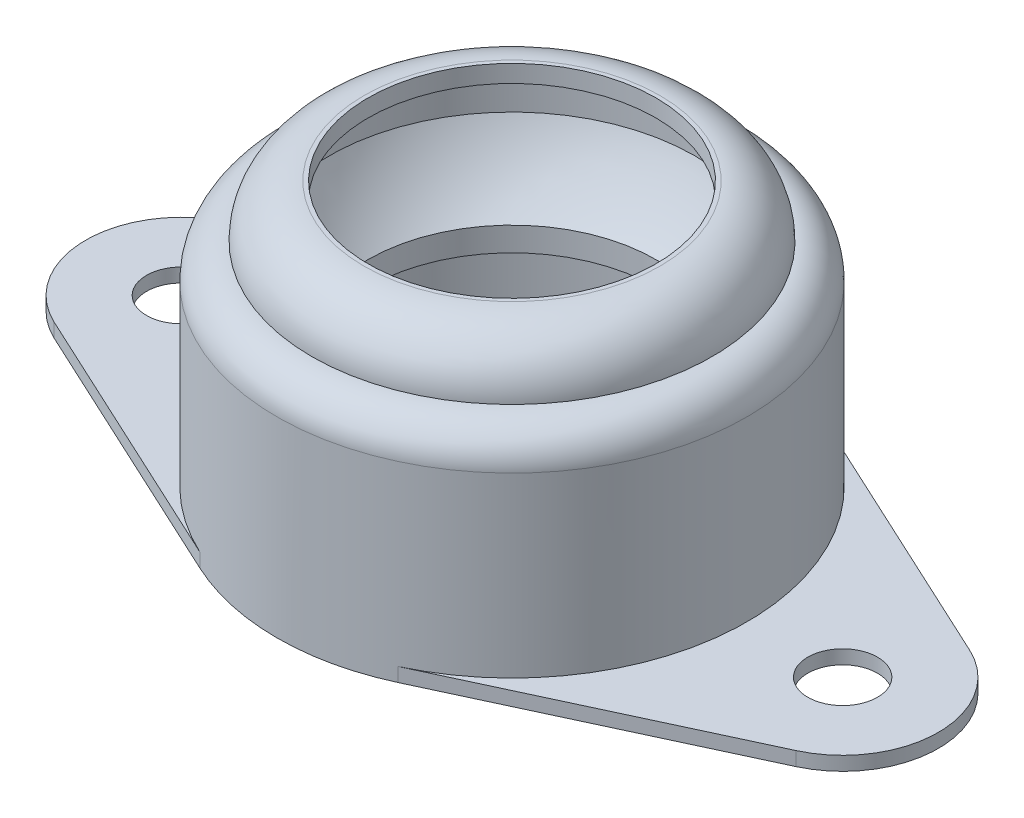
SolidWorks part; units mm, degrees
ref_plane "前视基准面" through (0, 0, 0) normal (0, 0, 1) x (1, 0, 0)
ref_plane "上视基准面" through (0, 0, 0) normal (0, 1, 0) x (1, 0, 0)
ref_plane "右视基准面" through (0, 0, 0) normal (1, 0, 0) x (0, 0, -1)
sketch "草图1" plane through (0, 0, 0) normal (0, 0, 1) x (1, 0, 0)
  line L0 (0, 30.5884) -> (0, -31.2764) construction
  line L1 (0, 0) -> (12.5, 0)
  line L2 (12.5, 0) -> (13.5, 0)
  line L3 (13.5, 0) -> (13.5, 13)
  line L4 (13.5, 13) -> (11.5, 13)
  line L5 (11.5, 13) -> (11.5, 16)
  line L6 (11.5, 16) -> (7.9375, 16)
  line L7 (0, 0) -> (0, 1)
  line L8 (0, 1) -> (12.5, 1)
  line L9 (12.5, 1) -> (12.5, 12)
  line L10 (12.5, 12) -> (10.5, 12)
  line L11 (10.5, 12) -> (10.5, 15)
  line L12 (10.5, 15) -> (7.9375, 15)
  line L13 (0, 24.0002) -> (0, 0)
  arc A1 (0, 7.9998) -> (0, 24.0002) centre (0, 16) ccw
  dimension "D1" = 12.5
  dimension "D2" = 13
revolve "旋转1" add sketch "草图1" angle 360 about L0 region at (0.2093, 0.5, 0) region at (3.3954, 16, 0)
fillet "圆角1" radius 2 1 edges at (0, 13, 13.5)
fillet "圆角2" radius 3 1 edges at (0, 16, 11.5)
sketch "草图2" plane through (0, 0, 0) normal (0, -1, 0) x (1, 0, 0)
  line L1 (5.6842, 12.245) -> (21.3158, 4.9887)
  line L2 (19, 0) -> (30.1808, 0) construction
  line L3 (5.6842, -12.245) -> (21.3158, -4.9887)
  line L4 (0, 11.8551) -> (0, -10.745) construction
  line L5 (-5.6842, -12.245) -> (-21.3158, -4.9887)
  line L6 (-5.6842, 12.245) -> (-21.3158, 4.9887)
  circle A0 centre (19, 0) radius 2
  arc A1 (21.3158, -4.9887) -> (21.3158, 4.9887) centre (19, 0) ccw
  circle A2 centre (0, 0) radius 13.5 construction
  arc A3 (5.6842, 12.245) -> (-5.6842, 12.245) centre (0, 0) ccw
  arc A4 (-5.6842, 12.245) -> (5.6842, 12.245) centre (0, 0) cw
  arc A5 (-21.3158, -4.9887) -> (-21.3158, 4.9887) centre (-19, 0) cw
  circle A6 centre (-19, 0) radius 2
  arc A7 (-5.6842, -12.245) -> (5.6842, -12.245) centre (0, 0) ccw
  arc A8 (5.6842, -12.245) -> (-5.6842, -12.245) centre (0, 0) cw
  circle M4 centre (0, 0) radius 13.5
extrude "凸台-拉伸1" add sketch "草图2" against normal blind 0.8 contours A5 L5 L6 A6 M4 | L3 A1 L1 A0 M4 region at (16.8441, 0, 0) region at (-16.8441, 0, 0)
sketch "草图3" plane through (0, 0, 0) normal (0, 0, 1) x (1, 0, 0)
  line L0 (0, 0) -> (12.5, 0)
  line L1 (5.6842, 0) -> (21.3158, 0) construction
  line L2 (12.5, 0) -> (12.5, 10.5)
  line L3 (12, 11) -> (11.8233, 11)
  line L4 (13.5, 11) -> (-13.5, 11) construction
  line L5 (0, 3.4601) -> (0, 0)
  arc A0 (0, 3.4601) -> (11.3699, 10.7109) centre (0, 16) ccw
  arc A1 (12.5, 10.5) -> (12, 11) centre (12, 10.5) ccw
  arc A2 (11.3699, 10.7109) -> (11.8233, 11) centre (11.8233, 10.5) cw
  point P15 (11.5, 11)
  dimension "D1" = 0.5
  dimension "D2" = 0.5
revolve "切除-旋转1" cut sketch "草图3" angle 360 about L5
sketch "草图4" plane through (0, 0, 0) normal (0, 0, 1) x (1, 0, 0)
  line L0 (12, 11) -> (11.8233, 11)
  line L1 (0, 3.4601) -> (0, 4.4601)
  line L2 (10.8575, 12.0903) -> (10.8575, 11.1747)
  line L3 (10.8575, 11.1747) -> (12.5, 11.1747)
  line L4 (12.5, 11.1747) -> (12.5, 10.5)
  arc A0 (12.5, 10.5) -> (12, 11) centre (12, 10.5) ccw
  arc A1 (12.5, 10.5) -> (12, 11) centre (12, 10.5) ccw construction
  arc A2 (11.8233, 11) -> (11.3699, 10.7109) centre (11.8233, 10.5) ccw
  arc A3 (11.8233, 11) -> (11.3699, 10.7109) centre (11.8233, 10.5) ccw construction
  arc A4 (0, 3.4601) -> (11.3699, 10.7109) centre (0, 16) ccw
  arc A5 (0, 4.4601) -> (10.8575, 12.0903) centre (0, 16) ccw
revolve "旋转2" add sketch "草图4" angle 360 about L1 region at (11.9116, 11.1519, 0)
fillet "圆角3" radius 1 1 edges at (0, 0, 12.5)
sketch "草图5" plane through (0, 16, 0) normal (0, 1, 0) x (1, 0, 0)
  circle A0 centre (0, 0) radius 8.2691
extrude "切除-拉伸1" cut sketch "草图5" along normal mid plane 30
